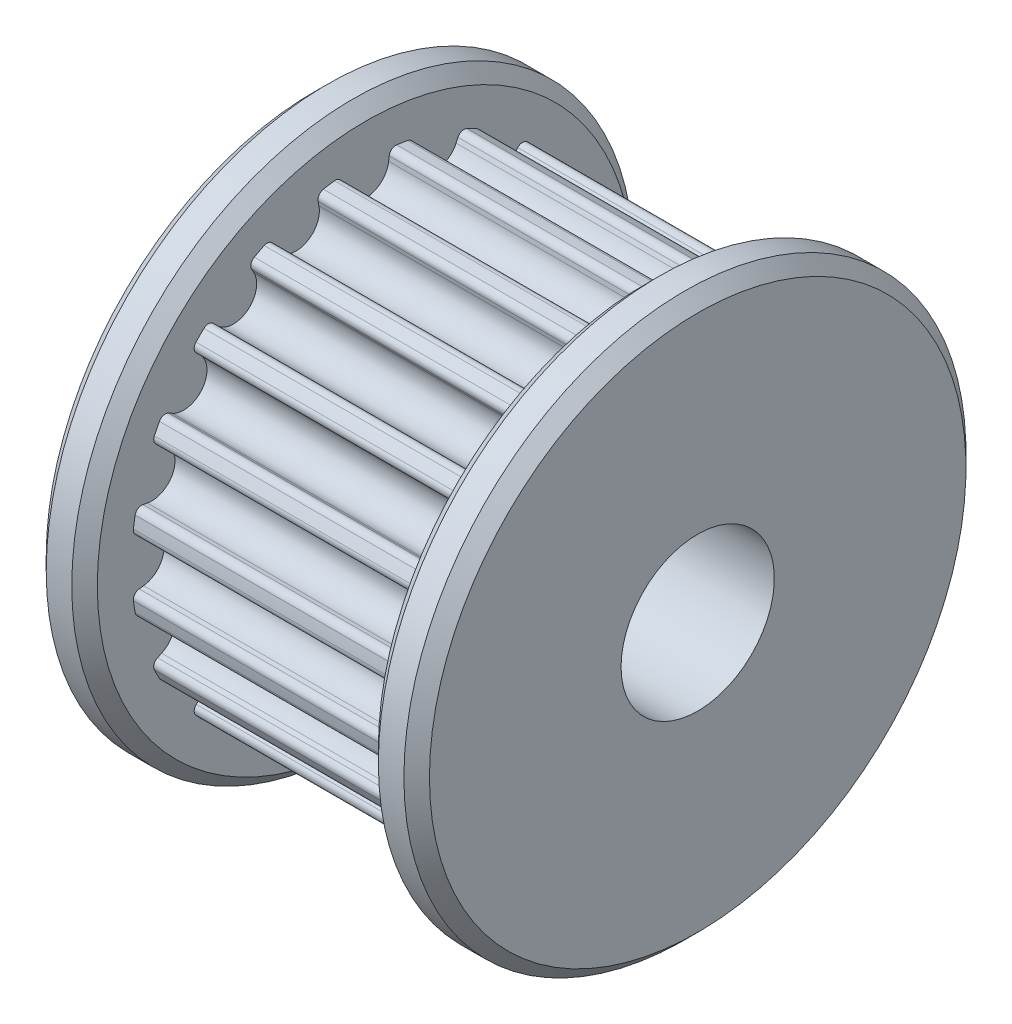
SolidWorks part; units mm, degrees
ref_plane "前视基准面" through (0, 0, 0) normal (0, 0, 1) x (1, 0, 0)
ref_plane "上视基准面" through (0, 0, 0) normal (0, 1, 0) x (1, 0, 0)
ref_plane "右视基准面" through (0, 0, 0) normal (1, 0, 0) x (0, 0, -1)
sketch "草图1" plane through (0, 0, 0) normal (0, 0, 1) x (1, 0, 0)
  line L0 (0, 0) -> (64.8368, 0) construction
  line L1 (0, 3) -> (0, 9.169)
  line L2 (0, 9.169) -> (11, 9.169)
  line L5 (11, 9.169) -> (11, 3)
  line L6 (11, 3) -> (0, 3)
  dimension "L" = 11
  dimension "d" = 6
  dimension "da" = 18.338
revolve "旋转1" add sketch "草图1" angle 360 about L0
sketch "草图6" plane through (0, 0, 0) normal (1, 0, 0) x (0, 0, -1)
  line L0 (0, 0) -> (0, 30.6512) construction
  line L1 (0.9246, 8.8618) -> (0.9032, 8.6881)
  line L2 (1.4743, 9.0497) -> (1.671, 10.6513)
  line L3 (-1.4743, 9.0497) -> (-1.671, 10.6513)
  line L4 (-0.9246, 8.8618) -> (-0.9032, 8.6881)
  circle A0 centre (0, 0) radius 9.169 construction
  circle A1 centre (0, 0) radius 7.889 construction
  arc A2 (-0.9032, 8.6881) -> (0.9032, 8.6881) centre (0, 8.799) ccw
  arc A3 (1.671, 10.6513) -> (-1.671, 10.6513) centre (0, 0) ccw
  arc A4 (0.9246, 8.8618) -> (1.2171, 9.0879) centre (1.1826, 8.8302) cw
  arc A5 (1.2171, 9.0879) -> (1.4743, 9.0497) centre (0, 0) cw
  arc A6 (-1.2171, 9.0879) -> (-1.4743, 9.0497) centre (0, 0) ccw
  arc A7 (-0.9246, 8.8618) -> (-1.2171, 9.0879) centre (-1.1826, 8.8302) ccw
  point P7 (0, 1.9)
  point P8 (0, 29.3712)
  point P15 (0.9561, 9.119)
  dimension "D1" = 15.778
  dimension "ra" = 0.26
  dimension "rf" = 0.91
  dimension "hg" = 1.28
  dimension "D3" = 0.26
  dimension "D4" = 1.6136
  dimension "angle" = 14
  dimension "bw" = 1.9
extrude "切除-拉伸2" cut sketch "草图6" along normal up to next
ref_axis "基准轴1" through (-1.4, 0, 0) along (1, 0, 0)
pattern_circular "阵列(圆周)3" count 20 over 360 about axis through (-1.4, 0, 0) along (1, 0, 0) of "切除-拉伸2"
sketch "草图7" plane through (0, 0, 0) normal (-1, 0, 0) x (0, 0, 1)
  circle A0 centre (0, 0) radius 11
  circle A1 centre (0, 0) radius 3 construction
  circle A2 centre (0, 0) radius 3
  dimension "D1" = 22
extrude "凸台-拉伸1" add sketch "草图7" along normal blind 2
extrude "凸台-拉伸2" add sketch "草图7<2>" against normal blind 2 from surface starting at face at (11, 0, 3)
sketch "草图7<2>" plane through (0, 0, 0) normal (-1, 0, 0) x (0, 0, 1) same geometry as "草图7"
chamfer "倒角1" distance 0.5 angle 45 4 edges at (13, 0, 11) (11, 0, 11) (0, 0, 11) (-2, 0, 11)
equation "\"D1@草图6\" = \"da@草图1\"  - \"hg@草图6\" - \"hg@草图6\""
equation "\"D3@草图6\" = \"ra@草图6\""
